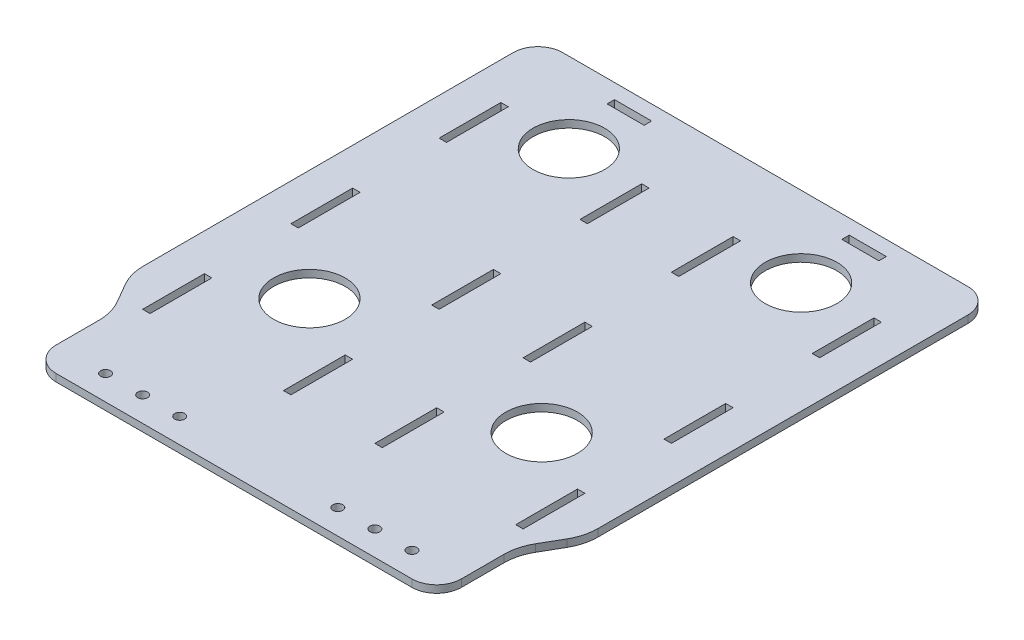
SolidWorks part; units mm, degrees
material "C-玻璃纤维"
ref_plane "前视基准面" through (0, 0, 0) normal (0, 0, 1) x (1, 0, 0)
ref_plane "上视基准面" through (0, 0, 0) normal (0, 1, 0) x (1, 0, 0)
ref_plane "右视基准面" through (0, 0, 0) normal (1, 0, 0) x (0, 0, -1)
other "Configuration Table"
sketch "草图1" plane through (0, 0, 0) normal (0, 1, 0) x (1, 0, 0)
  line L0 (47, 50) -> (47, -88.016) construction
  line L1 (-35, 37.5) -> (35, 37.5)
  line L2 (-35, 37.5) -> (-35, -37.5)
  line L3 (-35, -37.5) -> (35, -37.5)
  line L4 (35, 37.5) -> (35, -37.5)
  line L5 (-35, 37.5) -> (35, -37.5) construction
  line L6 (-35, -37.5) -> (35, 37.5) construction
  line L7 (0, 40) -> (0, -19.5313) construction
  line L8 (35, -37.5) -> (59, -37.5)
  line L9 (35, -37.5) -> (35, 37.5)
  line L10 (35, 37.5) -> (59, 37.5)
  line L11 (47, -37.5) -> (47, 37.5)
  line L12 (94, 40) -> (94, -19.5313) construction
  line L13 (129, -37.5) -> (59, 37.5) construction
  line L14 (129, 37.5) -> (59, -37.5) construction
  line L15 (59, -37.5) -> (59, 37.5)
  line L16 (59, 37.5) -> (59, -37.5)
  line L17 (129, -37.5) -> (59, -37.5)
  line L18 (129, 37.5) -> (129, -37.5)
  line L19 (129, 37.5) -> (59, 37.5)
  line L21 (-35, 37.5) -> (129, 37.5)
  line L22 (-35, 37.5) -> (-35, 177.5)
  line L23 (-35, 177.5) -> (129, 177.5)
  line L24 (129, 37.5) -> (129, 177.5)
  circle A0 centre (0, 40) radius 14.5
  circle A4 centre (94, 40) radius 14.5
  circle A5 centre (0, 145) radius 14.5
  circle A6 centre (94, 145) radius 14.5
  point P0 (0, 0)
  point P26 (94, 0)
  dimension "D3" = 29
  dimension "D4" = 40
  dimension "D8" = 105
  dimension "D1" = 70
  dimension "D2" = 75
  dimension "D5" = 140
  dimension "D6" = 12
  dimension "D7" = 2
extrude "凸台-拉伸1" add sketch "草图1" along normal blind 3 contours L19 A4 L24 L23 L22 L1 A0 L10 A5 A6 | A0 L1 L2 L3 L4 | L19 A4 L15 L17 L18 | L8 L11 L10 L4 | L8 L15 L10 L11 region at (47, 0, -107.5432) region at (0, 0, 1.6792) region at (41, 0, 0) region at (53, 0, 0) region at (94, 0, 1.6792)
sketch "草图2" plane through (0, 3, 0) normal (0, 1, 0) x (1, 0, 0)
  line L0 (-45, -27.5) -> (0, -27.5) construction
  line L1 (-35, -37.5) -> (129, -37.5) construction
  line L2 (0, -14.5781) -> (0, -41.2879) construction
  line L3 (47, 2.5) -> (47, -37.5) construction
  line L5 (94, -14.5781) -> (94, -41.2879) construction
  line L6 (139, -27.5) -> (94, -27.5) construction
  circle A0 centre (0, -27.5) radius 2
  circle A1 centre (-15, -27.5) radius 2
  circle A2 centre (15, -27.5) radius 2
  circle A3 centre (79, -27.5) radius 2
  circle A4 centre (109, -27.5) radius 2
  circle A5 centre (94, -27.5) radius 2
  dimension "D2" = 4
  dimension "D3" = 15
  dimension "D1" = 10
extrude "切除-拉伸1" cut sketch "草图2" against normal blind 3
sketch "草图3" plane through (0, 3, 0) normal (0, 1, 0) x (1, 0, 0)
  line L0 (-35, 177.5) -> (129, 177.5) construction
  line L1 (27, 147.5) -> (30, 147.5)
  line L2 (27, 147.5) -> (27, 122.5)
  line L3 (27, 122.5) -> (30, 122.5)
  line L4 (30, 147.5) -> (30, 122.5)
  line L5 (-35, -37.5) -> (-35, 177.5) construction
  line L6 (47, -37.5) -> (47, 12.5458) construction
  line L7 (-35, -37.5) -> (129, -37.5) construction
  line L8 (64, 147.5) -> (64, 122.5)
  line L9 (67, 122.5) -> (64, 122.5)
  line L10 (67, 147.5) -> (67, 122.5)
  line L11 (67, 147.5) -> (64, 147.5)
  line L12 (27, 87.5) -> (27, 62.5)
  line L13 (27, 87.5) -> (30, 87.5)
  line L14 (30, 87.5) -> (30, 62.5)
  line L15 (27, 62.5) -> (30, 62.5)
  line L16 (64, 87.5) -> (64, 62.5)
  line L17 (67, 62.5) -> (64, 62.5)
  line L18 (67, 87.5) -> (67, 62.5)
  line L19 (67, 87.5) -> (64, 87.5)
  line L20 (27, 27.5) -> (27, 2.5)
  line L21 (27, 27.5) -> (30, 27.5)
  line L22 (30, 27.5) -> (30, 2.5)
  line L23 (27, 2.5) -> (30, 2.5)
  line L24 (64, 27.5) -> (64, 2.5)
  line L25 (67, 2.5) -> (64, 2.5)
  line L26 (67, 27.5) -> (67, 2.5)
  line L27 (67, 27.5) -> (64, 27.5)
  line L28 (0, 147.1795) -> (0, 37.0423) construction
  line L29 (-27, 2.5) -> (-30, 2.5)
  line L30 (-30, 27.5) -> (-30, 2.5)
  line L31 (-27, 27.5) -> (-30, 27.5)
  line L32 (-27, 27.5) -> (-27, 2.5)
  line L33 (-27, 62.5) -> (-30, 62.5)
  line L34 (-30, 87.5) -> (-30, 62.5)
  line L35 (-27, 87.5) -> (-30, 87.5)
  line L36 (-27, 87.5) -> (-27, 62.5)
  line L37 (-30, 147.5) -> (-30, 122.5)
  line L38 (-27, 122.5) -> (-30, 122.5)
  line L39 (-27, 147.5) -> (-27, 122.5)
  line L40 (-27, 147.5) -> (-30, 147.5)
  line L41 (121, 147.5) -> (124, 147.5)
  line L42 (121, 147.5) -> (121, 122.5)
  line L43 (121, 122.5) -> (124, 122.5)
  line L44 (124, 147.5) -> (124, 122.5)
  line L45 (121, 87.5) -> (121, 62.5)
  line L46 (121, 87.5) -> (124, 87.5)
  line L47 (124, 87.5) -> (124, 62.5)
  line L48 (121, 62.5) -> (124, 62.5)
  line L49 (121, 27.5) -> (121, 2.5)
  line L50 (121, 27.5) -> (124, 27.5)
  line L51 (124, 27.5) -> (124, 2.5)
  line L52 (121, 2.5) -> (124, 2.5)
  dimension "D1" = 3
  dimension "D2" = 25
  dimension "D3" = 30
  dimension "D4" = 62
  dimension "D6" = 60
  dimension "D5" = 3
extrude "切除-拉伸2" cut sketch "草图3" against normal blind 10
sketch "草图4" plane through (0, 3, 0) normal (0, 1, 0) x (1, 0, 0)
  line L0 (-35, 177.5) -> (129, 177.5) construction
  line L1 (-8, 171.5) -> (7, 171.5)
  line L2 (-8, 171.5) -> (-8, 168.5)
  line L3 (-8, 168.5) -> (7, 168.5)
  line L4 (7, 171.5) -> (7, 168.5)
  line L5 (47, 177.5) -> (47, 163.5589) construction
  line L6 (102, 168.5) -> (87, 168.5)
  line L7 (87, 171.5) -> (87, 168.5)
  line L8 (102, 171.5) -> (87, 171.5)
  line L9 (102, 171.5) -> (102, 168.5)
  point P6 (47, 177.5)
  dimension "D1" = 3
  dimension "D2" = 15
  dimension "D3" = 40
  dimension "D4" = 6
extrude "切除-拉伸3" cut sketch "草图4" against normal blind 10
sketch "草图6" plane through (0, 3, 0) normal (0, 1, 0) x (1, 0, 0)
  line L0 (-35, -37.5) -> (-35, 177.5) construction
  line L1 (-35, 177.5) -> (-45, 177.5)
  line L2 (-35, 177.5) -> (-35, -12.5)
  line L3 (-35, -12.5) -> (-45, -12.5)
  line L4 (-45, 177.5) -> (-45, -12.5)
  line L5 (47, -37.5) -> (47, 41.2325) construction
  line L6 (-35, -37.5) -> (129, -37.5) construction
  line L7 (129, -12.5) -> (139, -12.5)
  line L8 (139, 177.5) -> (139, -12.5)
  line L9 (129, 177.5) -> (139, 177.5)
  line L10 (129, 177.5) -> (129, -12.5)
  dimension "D1" = 10
  dimension "D2" = 25
extrude "凸台-拉伸2" add sketch "草图6" against normal blind 3
chamfer "倒角1" distance 25 angle 30 2 edges at (139, 1.5, 12.5) (-45, 1.5, 12.5) first distance on face at (139, 1.5, -82.5) first distance on face at (-45, 1.5, -82.5)
fillet "圆角3" radius 20 4 edges at (-45, 1.5, -12.5) (139, 1.5, -12.5) (129, 1.5, 4.8205) (-35, 1.5, 4.8205)
fillet "圆角4" radius 10 4 edges at (-35, 1.5, 37.5) (129, 1.5, 37.5) (139, 1.5, -177.5) (-45, 1.5, -177.5)
